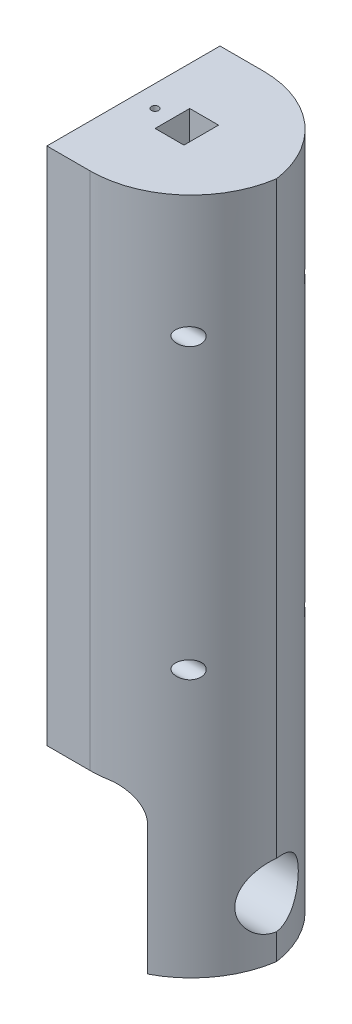
SolidWorks part; units mm, degrees
ref_plane "Plan de face" through (0, 0, 0) normal (0, 0, 1) x (1, 0, 0)
ref_plane "Plan de dessus" through (0, 0, 0) normal (0, 1, 0) x (1, 0, 0)
ref_plane "Plan de droite" through (0, 0, 0) normal (1, 0, 0) x (0, 0, -1)
sketch "Esquisse1" plane through (0, 0, 0) normal (0, 0, 1) x (1, 0, 0)
  line L0 (-50, 175) -> (-50, -55)
  line L1 (-50, -55) -> (-31, -55)
  line L2 (-31, -55) -> (-31, 0)
  line L3 (-31, 0) -> (31, 0)
  line L4 (31, 0) -> (31, -55)
  line L5 (31, -55) -> (50, -55)
  line L6 (50, -55) -> (50, 175)
  line L7 (50, 175) -> (-50, 175)
  line L8 (0, 0) -> (50, 0) construction
  line L9 (0, 0) -> (0, 175) construction
  point P14 (0, 0)
  dimension "D1" = 230
  dimension "D2" = 100
  dimension "D3" = 62
  dimension "D4" = 55
extrude "Boss.-Extru.1" add sketch "Esquisse1" along normal blind 60
fillet "Congé4" radius 35 1 edges at (-50, 60, 60)
fillet "Congé5" radius 35 1 edges at (-50, 60, 0)
fillet "Congé6" radius 35 2 edges at (50, 60, 0) (50, 60, 60)
fillet "Congé12" radius 10 2 edges at (-31, 0, 29.6462) (31, 0, 30)
sketch "Esquisse3" plane through (31, 0, 0) normal (-1, 0, 0) x (0, 0, 1)
  line L0 (30, -55) -> (30, -35) construction
  line L1 (56.1288, -55) -> (3.8712, -55) construction
  circle A1 centre (30, -35) radius 11
  dimension "D1" = 22
  dimension "D2" = 20
extrude "Enlèv. mat.-Extru.4" cut sketch "Esquisse3" against normal blind 50
sketch "Esquisse5" plane through (0, 175, 0) normal (0, 1, 0) x (1, 0, 0)
  line L0 (0, -60) -> (0, 0)
  line L1 (15, -60) -> (-15, -60) construction
  arc A0 (0, -60) -> (0, 0) centre (-29.0756, -30) cw
extrude "Enlèv. mat.-Extru.8" cut sketch "Esquisse5" against normal blind 251
sketch "Esquisse6" plane through (0, 0, 0) normal (-1, 0, 0) x (0, 0, 1)
  line L0 (30, 175) -> (30, 0) construction
  line L1 (60, 175) -> (0, 175) construction
  line L2 (60, 0) -> (0, 0) construction
  line L4 (60, 0) -> (60, 175) construction
  line L5 (60, 87.5) -> (0, 87.5) construction
  line L6 (0, 0) -> (0, 175) construction
  circle A0 centre (10, 137.5) radius 2
  circle A1 centre (50, 137.5) radius 2
  circle A2 centre (50, 37.5) radius 2
  circle A3 centre (10, 37.5) radius 2
  dimension "D1" = 40
  dimension "D2" = 50
  dimension "D3" = 4
extrude "Enlèv. mat.-Extru.9" cut sketch "Esquisse6" against normal blind 58
sketch "Esquisse13" plane through (0, 175, 0) normal (0, 1, 0) x (1, 0, 0)
  line L0 (0, 0) -> (0, -60) construction
  line L1 (0, -30) -> (49.641, -30) construction
  line L2 (13.5, -24) -> (13.5, -36)
  line L3 (13.5, -36) -> (23.5, -36)
  line L4 (23.5, -36) -> (23.5, -24)
  line L5 (23.5, -24) -> (13.5, -24)
  point P9 (13.5, -30)
  dimension "D1" = 13.5
  dimension "D2" = 12
  dimension "D3" = 10
extrude "Enlèv. mat.-Extru.15" cut sketch "Esquisse13" against normal through all
shell "Coque1" thickness 5 removed face at (18.5, 175, 30)
ref_plane "Plan2" through (49.641, 0, 0) normal (-1, 0, 0) x (0, 0, 1)
sketch "Esquisse11" plane through (49.641, 0, 0) normal (-1, 0, 0) x (0, 0, 1)
  circle A0 centre (50, 37.5) radius 2 construction
  circle A1 centre (50, 137.5) radius 2 construction
  circle A2 centre (50, 37.5) radius 2 construction
  circle A3 centre (50, 137.5) radius 2 construction
  circle A4 centre (10, 137.5) radius 2 construction
  circle A5 centre (10, 37.5) radius 2 construction
  circle A6 centre (10, 137.5) radius 2 construction
  circle A7 centre (10, 37.5) radius 2 construction
  circle A8 centre (50, 137.5) radius 3
  circle A9 centre (10, 137.5) radius 3
  circle A10 centre (50, 37.5) radius 3
  circle A11 centre (10, 37.5) radius 3
  dimension "D1" = 1
  dimension "D2" = 1
  dimension "D3" = 1
  dimension "D4" = 1
extrude "Enlèv. mat.-Extru.14" cut sketch "Esquisse11" along normal blind 20
sketch "Esquisse12" plane through (0, 175, 0) normal (0, 1, 0) x (1, 0, 0)
  line L0 (15, 0) -> (0, 0) construction
  line L1 (0, -60) -> (0, 0) construction
  line L2 (13.5, -24) -> (13.5, -36) construction
  line L3 (15, -60) -> (0, -60) construction
  line L4 (15, 0) -> (0, 0)
  line L5 (0, -60) -> (0, 0)
  line L7 (15, -60) -> (0, -60)
  line L9 (13.5, -36) -> (23.5, -36) construction
  line L10 (23.5, -36) -> (23.5, -24) construction
  line L11 (23.5, -24) -> (13.5, -24) construction
  line L12 (13.5, -24) -> (13.5, -36)
  line L13 (13.5, -36) -> (23.5, -36)
  line L14 (23.5, -36) -> (23.5, -24)
  line L15 (23.5, -24) -> (13.5, -24)
  arc A1 (15, -60) -> (49.641, -30) centre (15, -25) ccw construction
  arc A2 (49.641, -30) -> (15, 0) centre (15, -35) ccw construction
  arc A4 (15, -60) -> (49.641, -30) centre (15, -25) ccw
  arc A5 (49.641, -30) -> (15, 0) centre (15, -35) ccw
extrude "Boss.-Extru.2" add sketch "Esquisse12" along normal blind 5
ref_plane "Plan3" through (0, 0, 30) normal (0, 0, -1) x (0, -1, 0)
sketch "Esquisse14" plane through (0, 180, 0) normal (0, 1, 0) x (1, 0, 0)
  line L0 (0, 0) -> (0, -60) construction
  line L1 (0, -30) -> (7.5, -30) construction
  circle A0 centre (7.5, -30) radius 1.25
  dimension "D2" = 2.5
  dimension "D1" = 7.5
extrude "Enlèv. mat.-Extru.16" cut sketch "Esquisse14" against normal blind 4 contours A0
